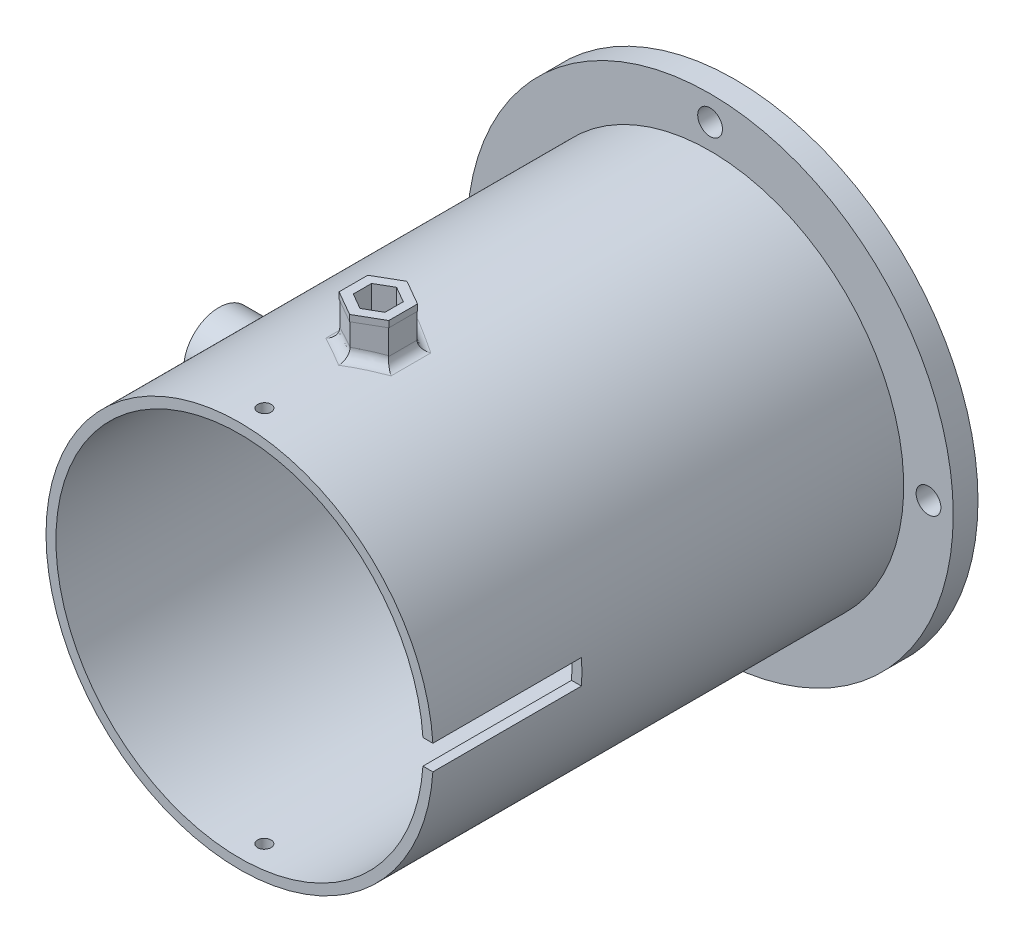
SolidWorks part; units mm, degrees
material "ABS"
ref_plane "Front Plane" through (0, 0, 0) normal (0, 0, 1) x (1, 0, 0)
ref_plane "Top Plane" through (0, 0, 0) normal (0, 1, 0) x (1, 0, 0)
ref_plane "Right Plane" through (0, 0, 0) normal (1, 0, 0) x (0, 0, -1)
sketch "Sketch1" plane through (0, 0, 0) normal (0, 0, 1) x (1, 0, 0)
  circle A0 centre (0, 0) radius 49.657
  circle A1 centre (0, 0) radius 47.117
  dimension "D1" = 2.54
  dimension "D2" = 94.234
extrude "Boss-Extrude1" add sketch "Sketch1" along normal mid plane 127
sketch "Sketch2" plane through (0, 0, -63.5) normal (0, 0, -1) x (-1, 0, 0)
  circle A1 centre (0, 0) radius 49.657 construction
  circle A2 centre (0, 0) radius 49.657
  circle A4 centre (0, 0) radius 62.357
  dimension "D1" = 12.7
extrude "Boss-Extrude2" add sketch "Sketch2" against normal blind 6.35
hole_wizard "#8-32 Tapped Hole1" positions "Sketch4" profile "Sketch5" tap size "#8-32" standard "ANSI Inch" end condition through all
sketch "Sketch4" plane through (0, 0, 0) normal (0, 1, 0) x (1, 0, 0)
  line L0 (-49.657, -63.5) -> (49.657, -63.5) construction
  point P0 (0, -57.15)
  dimension "D1" = 6.35
sketch "Sketch5" plane through (0, 0, 57.15) normal (1, 0, 0) x (0, 0, -1)
  line L0 (0, 0) -> (0, 62.357)
  line L1 (0, 62.357) -> (1.7272, 62.357)
  line L2 (1.7272, 62.357) -> (1.7272, 0.9906)
  line L3 (1.7272, 0.9906) -> (2.7178, 0)
  line L5 (2.7178, 0) -> (0, 0)
  line L6 (-1.7272, 0.9906) -> (-2.7178, 0) construction
  line L11 (0, -6.35) -> (0, 107.95) construction
  dimension "Thru Tap Drill Dia." = 3.4544
  dimension "Thru Tap Drill Depth" = 62.357
  dimension "Near C'Sink Dia." = 5.4356
  dimension "Near C'Sink Angle" = 90
cosmetic thread "Hole Thread1" parameters "D1"=3.048, "D2"=4.1656
mirror "Mirror1" about plane through (0, 0, 0) normal (0, 1, 0) of "#8-32 Tapped Hole1"
sketch "Sketch6" plane through (0, 0, 0) normal (0, 0, 1) x (1, 0, 0)
  circle A4 centre (0, 0) radius 56.007
  circle A5 centre (0, 0) radius 56.007
  dimension "D1" = 6.35
hole_wizard "1/4 (0.2500) Dowel Hole1" positions "Sketch8" profile "Sketch9" hole size "1/4" standard "ANSI Inch" end condition through all
sketch "Sketch8" plane through (0, 0, -57.15) normal (0, 0, 1) x (1, 0, 0)
  circle A0 centre (0, 0) radius 56.007 construction
  point P0 (-56.007, 0)
  point P4 (0, 56.007)
  point P6 (56.007, 0)
  point P8 (0, -56.007)
sketch "Sketch9" plane through (-56.007, 0, -57.15) normal (1, 0, 0) x (0, -1, 0)
  line L0 (0, 0) -> (0, 6.35)
  line L1 (0, 6.35) -> (3.175, 6.35)
  line L2 (3.175, 6.35) -> (3.175, 0)
  line L5 (3.175, 0) -> (0, 0)
  line L11 (0, -6.35) -> (0, 107.95) construction
  dimension "Thru Hole Dia." = 6.35
  dimension "Thru Hole Depth" = 6.35
sketch "Sketch10" plane through (0, 0, 0) normal (1, 0, 0) x (0, 0, -1)
  line L0 (-63.5, 49.657) -> (-63.5, -49.657) construction
  line L1 (-63.5, 3.175) -> (-25.4, 3.175)
  line L2 (-63.5, 3.175) -> (-63.5, -3.175)
  line L3 (-63.5, -3.175) -> (-25.4, -3.175)
  line L4 (-25.4, 3.175) -> (-25.4, -3.175)
  point P12 (-63.5, 0)
  dimension "D1" = 6.35
  dimension "D2" = 38.1
extrude "Cut-Extrude1" cut sketch "Sketch10" along normal through all
sketch "Sketch12" plane through (0, 0, 0) normal (1, 0, 0) x (0, 0, -1)
  circle A0 centre (0, 0) radius 3.175
  dimension "D1" = 6.35
extrude "Cut-Extrude3" cut sketch "Sketch12" against normal through all
sketch "Sketch13" plane through (0, 0, 0) normal (1, 0, 0) x (0, 0, -1)
  circle A2 centre (0, 0) radius 6.477
  circle A3 centre (0, 0) radius 9.017
  dimension "D4" = 12.954
  dimension "D5" = 2.54
extrude "Boss-Extrude3" add sketch "Sketch13" against normal blind 20.066 from offset 48.768 contours A3 A2 region at (0, 0, 8.762) offset against normal yes
sketch "Sketch14" plane through (0, 0, 0) normal (1, 0, 0) x (0, 0, -1)
  circle A1 centre (0, 0) radius 3.429
  circle A2 centre (0, 0) radius 3.175
  circle A3 centre (0, 0) radius 3.175 construction
  dimension "D1" = 0.254
extrude "Cut-Extrude4" cut sketch "Sketch14" against normal up to next
sketch "Sketch15" plane through (0, 0, 0) normal (0, 1, 0) x (1, 0, 0)
  line L0 (-49.657, -63.5) -> (49.5554, -63.5) construction
  circle A0 centre (0, -27.94) radius 1.905
  dimension "D1" = 3.81
  dimension "D2" = 35.56
extrude "Cut-Extrude5" cut sketch "Sketch15" along normal up to next
sketch "Sketch16" plane through (0, 0, 0) normal (0, 1, 0) x (1, 0, 0)
  line L1 (0, -35.1727) -> (6.2637, -31.5564)
  line L2 (6.2637, -31.5564) -> (6.2637, -24.3236)
  line L3 (6.2637, -24.3236) -> (0, -20.7073)
  line L4 (0, -20.7073) -> (-6.2637, -24.3236)
  line L5 (-6.2637, -24.3236) -> (-6.2637, -31.5564)
  line L6 (-6.2637, -31.5564) -> (0, -35.1727)
  line L7 (-4.064, -25.5936) -> (-4.064, -30.2864)
  line L8 (-4.064, -30.2864) -> (0, -32.6327)
  line L9 (0, -32.6327) -> (4.064, -30.2864)
  line L10 (4.064, -30.2864) -> (4.064, -25.5936)
  line L11 (4.064, -25.5936) -> (0, -23.2473)
  line L12 (0, -23.2473) -> (-4.064, -25.5936)
  circle A0 centre (0, -27.94) radius 1.905
  circle A1 centre (0, -27.94) radius 1.905 construction
  circle A2 centre (0, -27.94) radius 6.2637 construction
  circle A3 centre (0, -27.94) radius 4.064 construction
  dimension "D1" = 2.54
  dimension "D2" = 8.128
  dimension "D3" = 0
extrude "Boss-Extrude4" add sketch "Sketch16" along normal blind 8.89 from offset 49.022 contours L5 L6 L1 L2 L3 L4 L12 L11 L10 L9 L8 L7 region at (-3.0362, 0, 33.1988)
fillet "Fillet3" radius 2.54 6 edges at (-3.1381, 49.5577, 22.5191) (-6.2637, 49.2604, 27.94) (3.1381, 49.5577, 22.5191) (6.2637, 49.2604, 27.94) (-3.1381, 49.5577, 33.3609) (3.1381, 49.5577, 33.3609)
sketch "Sketch17" plane through (0, 57.912, 0) normal (0, 1, 0) x (1, 0, 0)
  line L0 (4.064, -30.2864) -> (4.064, -25.5936) construction
  line L1 (-4.064, -30.2864) -> (0, -32.6327)
  line L2 (0, -32.6327) -> (4.064, -30.2864)
  line L3 (4.064, -30.2864) -> (4.064, -25.5936)
  line L4 (4.064, -25.5936) -> (0, -23.2473)
  line L5 (0, -23.2473) -> (-4.064, -25.5936)
  line L6 (-4.064, -25.5936) -> (-4.064, -30.2864)
  line L7 (-6.3747, -31.6204) -> (0, -35.3009)
  line L8 (0, -35.3009) -> (6.3747, -31.6204)
  line L9 (6.3747, -31.6204) -> (6.3747, -24.2596)
  line L10 (6.3747, -24.2596) -> (0, -20.5791)
  line L11 (0, -20.5791) -> (-6.3747, -24.2596)
  line L12 (-6.3747, -24.2596) -> (-6.3747, -31.6204)
  circle A0 centre (0, -27.94) radius 4.064 construction
  circle A1 centre (0, -27.94) radius 6.3747 construction
extrude "Boss-Extrude5" add sketch "Sketch17" along normal blind 1.6256
fillet "Fillet4" radius 2.54 1 edges at (-49.6203, 1.9082, -8.8128)
